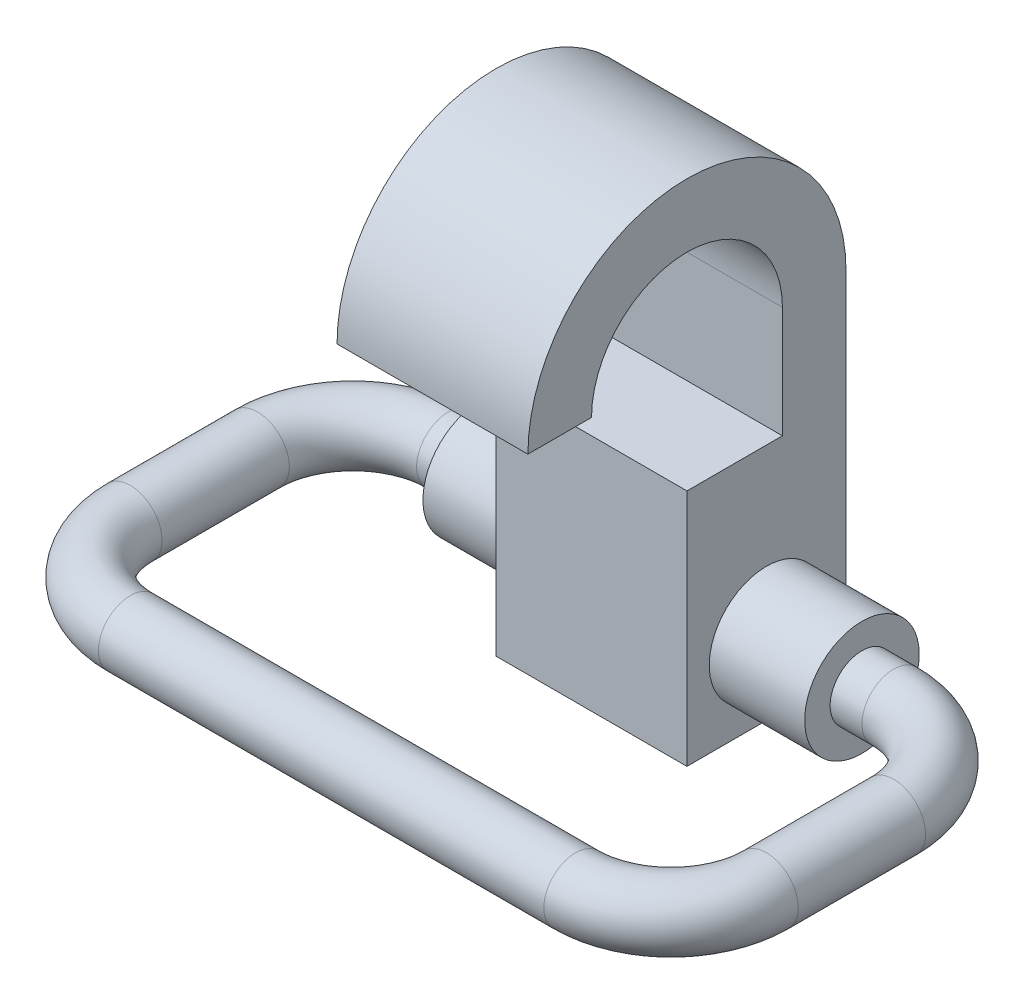
SolidWorks part; units mm, degrees
ref_plane "Plano frontal" through (0, 0, 0) normal (0, 0, 1) x (1, 0, 0)
ref_plane "Plano superior" through (0, 0, 0) normal (0, 1, 0) x (1, 0, 0)
ref_plane "Plano direito" through (0, 0, 0) normal (1, 0, 0) x (0, 0, -1)
sketch "Esboço1" plane through (0, 0, 0) normal (1, 0, 0) x (0, 0, -1)
  line L0 (-250, -375) -> (250, -375)
  line L1 (-250, -375) -> (-250, 375)
  line L2 (250, -375) -> (250, 375)
  line L3 (-250, 375) -> (250, 375)
  line L4 (-250, -375) -> (250, 375) construction
  line L5 (250, -375) -> (-250, 375) construction
  line L6 (250, -375) -> (0, -375) construction
  line L7 (0, -375) -> (0, -135) construction
  line L8 (250, 375) -> (50, 375) construction
  line L9 (50, 375) -> (250, 375)
  line L10 (50, 375) -> (50, 725)
  line L11 (250, 375) -> (250, 725)
  line L12 (50, 725) -> (250, 725)
  circle A0 centre (0, -135) radius 180
  circle A1 centre (0, -135) radius 100
  point P1 (0, 0)
  dimension "D4" = 360
  dimension "D5" = 200
  dimension "D1" = 750
  dimension "D2" = 500
  dimension "D3" = 240
  dimension "D6" = 200
  dimension "D7" = 350
extrude "Ressalto-extrusão2" add sketch "Esboço1" along normal blind 700 contours A1 region at (0, -135, 0)
extrude "Ressalto-extrusão6" add sketch "Esboço1<9>" along normal blind 600 contours A0 A1 region at (0, -135, 174.9088)
sketch "Esboço1<9>" plane through (0, 0, 0) normal (1, 0, 0) x (0, 0, -1) same geometry as "Esboço1"
extrude "Ressalto-extrusão7" add sketch "Esboço1<10>" along normal blind 300 contours L3 L1 L0 L2 A0 region at (0, 50.2954, 0)
sketch "Esboço1<10>" plane through (0, 0, 0) normal (1, 0, 0) x (0, 0, -1) same geometry as "Esboço1"
sketch "Esboço3" plane through (0, 375, 0) normal (0, 1, 0) x (1, 0, 0)
  line L0 (0, 250) -> (0, 50) construction
  line L1 (0, -250) -> (0, 250) construction
  line L3 (0, 50) -> (300, 50)
  line L4 (0, 50) -> (0, 250)
  line L5 (0, 250) -> (300, 250)
  line L6 (300, 50) -> (300, 250)
  dimension "D1" = 200
extrude "Ressalto-extrusão8" add sketch "Esboço3" along normal blind 350
sketch "Esboço5" plane through (300, 0, 0) normal (1, 0, 0) x (0, 0, -1)
  line L0 (50, 725) -> (-250, 725) construction
  line L1 (-750, 725) -> (-550, 725)
  line L2 (250, 725) -> (50, 725)
  arc A0 (50, 725) -> (-550, 725) centre (-250, 725) ccw
  arc A1 (250, 725) -> (-750, 725) centre (-250, 725) ccw
  dimension "D1" = 300
sketch "Esboço6" plane through (0, 0, 0) normal (-1, 0, 0) x (0, 0, 1)
  line L0 (-50, 725) -> (250, 725) construction
  line L1 (-250, 725) -> (-50, 725) construction
  line L2 (-50, 725) -> (-50, 375) construction
  dimension "D1" = 300
extrude "Ressalto-extrusão9" add sketch "Esboço5" against normal blind 300 contours A1 L1 A0 L2
sketch3d "3DSketch1" plane through (0, 0, 0) normal (0, 0, 1) x (1, 0, 0)
  dimension "D1" = 240
sketch "Esboço7" plane through (700, 0, 0) normal (1, 0, 0) x (0, 0, -1)
  point P0 (0, -135)
sketch "Esboço8" plane through (0, -135, 0) normal (0, -1, 0) x (-1, 0, 0)
  line L0 (-700, 0) -> (-700, -300) construction
  arc A0 (-700, 0) -> (-1000, -300) centre (-700, -300) ccw
  dimension "D1" = 300
sketch "Esboço9" plane through (700, 0, 0) normal (1, 0, 0) x (0, 0, -1)
  circle A0 centre (0, -135) radius 100
sweep "Varredura1" add profiles "Esboço9" path "Esboço8"
sketch "Esboço10" plane through (0, 0, 300) normal (0, 0, 1) x (1, 0, 0)
  circle A0 centre (1000, -135) radius 100
extrude "Ressalto-extrusão10" add sketch "Esboço10" along normal blind 400 contours A0
sketch "Esboço13" plane through (0, 0, 700) normal (0, 0, 1) x (1, 0, 0)
  point P0 (1000, -135)
sketch "Esboço14" plane through (0, -135, 0) normal (0, -1, 0) x (-1, 0, 0)
  line L0 (-1000, -700) -> (-700, -700) construction
  line L1 (-1100, -700) -> (-900, -700) construction
  arc A0 (-1000, -700) -> (-700, -1000) centre (-700, -700) ccw
  dimension "D1" = 300
sketch "Esboço15" plane through (0, 0, 700) normal (0, 0, 1) x (1, 0, 0)
  circle A0 centre (1000, -135) radius 100
sweep "Varredura2" add profiles "Esboço15" path "Esboço14"
sketch "Esboço17" plane through (700, 0, 0) normal (-1, 0, 0) x (0, 0, 1)
  circle A0 centre (1000, -135) radius 100
sketch "Esboço19" plane through (700, 0, 0) normal (-1, 0, 0) x (0, 0, 1)
extrude "Ressalto-extrusão11" add sketch "Esboço17" along normal blind 700
mirror "Espelhar1" of "Ressalto-extrusão11"
mirror "Espelhar2" of "Varredura2"
mirror "Espelhar3" of "Ressalto-extrusão10"
mirror "Espelhar4" of "Varredura1"
mirror "Espelhar5" of "Ressalto-extrusão2"
mirror "Espelhar6" of "Ressalto-extrusão6"
mirror "Espelhar7" of "Ressalto-extrusão9"
mirror "Espelhar8" about plane through (300, 0, 0) normal (1, 0, 0) of "Ressalto-extrusão2"
ref_plane "Plano1" through (0, -375, 250) normal (0, 1, 0) x (1, 0, 0)
sketch "Esboço21" plane through (0, 0, 0) normal (-1, 0, 0) x (0, 0, 1)
  line L0 (250, -375) -> (-250, -375) construction
  line L1 (250, 375) -> (-250, 375)
  line L2 (250, 375) -> (250, -375)
  line L3 (250, -375) -> (-250, -375)
  line L4 (-250, 375) -> (-250, -375)
  line L5 (-250, -375) -> (-250, 725) construction
extrude "Ressalto-extrusão12" add sketch "Esboço21" along normal blind 300
sketch "Esboço22" plane through (0, 0, 0) normal (-1, 0, 0) x (0, 0, 1)
  line L1 (-250, 725) -> (-50, 725)
  line L2 (-250, 725) -> (-250, 375)
  line L3 (-250, 375) -> (-50, 375)
  line L4 (-50, 725) -> (-50, 375)
extrude "Ressalto-extrusão13" add sketch "Esboço22" along normal blind 300
